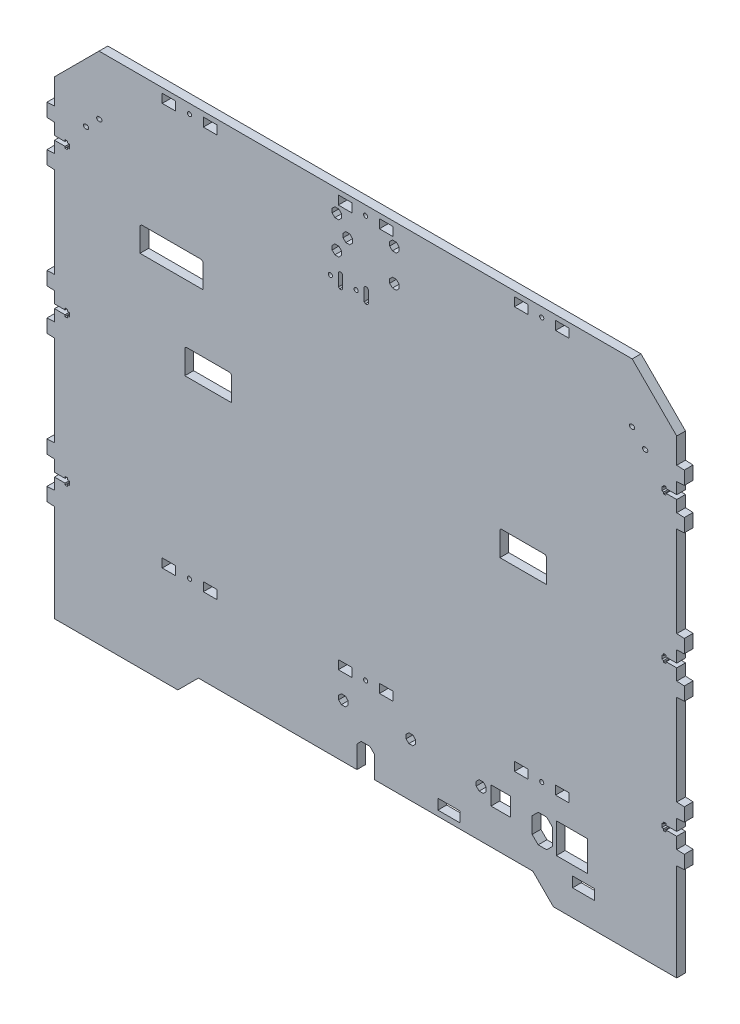
SolidWorks part; units mm, degrees
ref_plane "Front Plane" through (0, 0, 0) normal (0, 0, 1) x (1, 0, 0)
ref_plane "Top Plane" through (0, 0, 0) normal (0, 1, 0) x (1, 0, 0)
ref_plane "Right Plane" through (0, 0, 0) normal (1, 0, 0) x (0, 0, -1)
sketch "Sketch1" plane through (0, 0, 0) normal (0, 0, 1) x (1, 0, 0)
  line L0 (134.7234, -241.5755) -> (134.7234, -247.9755) construction
  line L1 (346.7221, 23.1293) -> (346.7221, 4.6501)
  line L2 (-107.2779, 23.1293) -> (-107.2779, 4.6501)
  line L4 (-96.3779, -120.3749) -> (-97.7779, -120.3749)
  line L5 (11.1227, 52.0245) -> (1.3227, 52.0245)
  line L6 (-28.6786, 45.6245) -> (-28.6786, 52.0245)
  line L7 (-23.7786, 52.0245) -> (-23.7786, 45.6245) construction
  line L8 (11.1227, 45.6245) -> (1.3227, 45.6245)
  line L9 (104.7221, -241.5755) -> (104.7221, -247.9755) construction
  line L10 (6.2227, 52.0245) -> (6.2227, 45.6245) construction
  line L11 (139.6234, -247.9755) -> (139.6234, -241.5755)
  line L12 (129.8234, -247.9755) -> (129.8234, -241.5755)
  line L13 (6.2227, 48.8245) -> (-23.7786, 48.8245) construction
  line L14 (-18.8786, 45.6245) -> (-18.8786, 52.0245)
  line L15 (-28.6786, 52.0245) -> (-18.8786, 52.0245)
  line L16 (1.3227, 45.6245) -> (1.3227, 52.0245)
  line L17 (-28.6786, 45.6245) -> (-18.8786, 45.6245)
  line L18 (11.1227, 45.6245) -> (11.1227, 52.0245)
  line L19 (134.7234, -244.7755) -> (104.7221, -244.7755) construction
  line L20 (139.6227, 52.0245) -> (129.8227, 52.0245)
  line L21 (139.6234, -247.9755) -> (129.8234, -247.9755)
  line L22 (99.8214, 45.6245) -> (99.8214, 52.0245)
  line L23 (104.7214, 52.0245) -> (104.7214, 45.6245) construction
  line L24 (139.6227, 45.6245) -> (129.8227, 45.6245)
  line L25 (109.6221, -247.9755) -> (109.6221, -241.5755)
  line L26 (134.7227, 52.0245) -> (134.7227, 45.6245) construction
  line L27 (99.8221, -241.5755) -> (109.6221, -241.5755)
  line L28 (139.6234, -241.5755) -> (129.8234, -241.5755)
  line L30 (268.1234, -241.5755) -> (258.3234, -241.5755)
  line L31 (99.8221, -247.9755) -> (99.8221, -241.5755)
  line L33 (99.8221, -247.9755) -> (109.6221, -247.9755)
  line L34 (346.722, -319.3255) -> (346.722, -248.4004)
  line L35 (268.1234, -247.9755) -> (268.1234, -241.5755)
  line L36 (314.2269, 55.6245) -> (-74.7828, 55.6245)
  line L37 (134.7227, 48.8245) -> (104.7214, 48.8245) construction
  line L38 (324.0971, 12.6745) -> (324.0971, 3.0745) construction
  line L39 (-84.6529, 12.6745) -> (-84.6529, 3.0745) construction
  line L40 (-74.7828, 55.6245) -> (-107.2779, 23.1293)
  line L41 (314.2269, 55.6245) -> (346.7221, 23.1293)
  line L42 (208.7504, -265.043) -> (199.3504, -274.343) construction
  line L43 (-84.6529, 12.6745) -> (-75.2529, 12.6745) construction
  line L46 (228.3221, -241.5755) -> (238.1221, -241.5755)
  line L47 (109.6214, 45.6245) -> (109.6214, 52.0245)
  line L48 (99.8214, 52.0245) -> (109.6214, 52.0245)
  line L49 (129.8227, 45.6245) -> (129.8227, 52.0245)
  line L50 (99.8214, 45.6245) -> (109.6214, 45.6245)
  line L51 (139.6227, 45.6245) -> (139.6227, 52.0245)
  line L52 (268.1227, 52.0245) -> (258.3227, 52.0245)
  line L53 (102.9071, 3.214) -> (102.0284, 4.0927)
  line L55 (118.6571, -6.0286) -> (118.6571, 3.214)
  line L56 (121.6571, 3.214) -> (121.6571, -6.0286)
  line L57 (228.3214, 45.6245) -> (228.3214, 52.0245)
  line L58 (233.2214, 52.0245) -> (233.2214, 45.6245) construction
  line L59 (228.3221, -247.9755) -> (238.1221, -247.9755)
  line L60 (233.2221, -241.5755) -> (233.2221, -247.9755) construction
  line L63 (258.3234, -247.9755) -> (258.3234, -241.5755)
  line L64 (6.2234, -241.5755) -> (6.2234, -247.9755) construction
  line L65 (-97.7779, -124.6249) -> (-99.5779, -124.6249)
  line L66 (-99.5779, -124.6249) -> (-99.5779, -123.3762)
  line L67 (-112.7779, -25.6249) -> (-107.2779, -25.3499)
  line L69 (-97.7779, -119.1249) -> (-99.5779, -119.1249)
  line L70 (-97.7779, -124.6249) -> (-97.7779, -123.3762)
  line L72 (-99.5779, -119.1249) -> (-99.5779, -120.3749)
  line L74 (-97.7779, -120.3749) -> (-97.7779, -119.1249)
  line L75 (-107.2779, -35.5999) -> (-107.2779, -101.7499)
  line L78 (-99.5779, -123.3762) -> (-107.2779, -123.3762)
  line L81 (-112.7779, -5.3249) -> (-107.2779, -5.5999)
  line L82 (-99.5779, -120.3749) -> (-107.2779, -120.3749)
  line L83 (346.7221, -208.1499) -> (346.7221, -141.9999)
  line L84 (-112.7779, 4.3751) -> (-107.2779, 4.6501)
  line L85 (-99.5779, -16.9762) -> (-107.2779, -16.9762)
  line L87 (-97.7779, -18.2249) -> (-97.7779, -16.9762)
  line L88 (-112.7779, -5.3249) -> (-112.7779, 4.3751)
  line L89 (-96.3779, -16.9762) -> (-97.7779, -16.9762)
  line L90 (-107.2779, -16.9762) -> (-107.2779, -25.3499)
  line L91 (-97.7779, -13.9749) -> (-97.7779, -12.7249)
  line L94 (-97.7779, -12.7249) -> (-99.5779, -12.7249)
  line L95 (-96.3779, -13.9749) -> (-97.7779, -13.9749)
  line L96 (-112.7779, -35.3249) -> (-112.7779, -25.6249)
  line L97 (-99.5779, -13.9749) -> (-107.2779, -13.9749)
  line L98 (-99.5779, -12.7249) -> (-99.5779, -13.9749)
  line L99 (-99.5779, -18.2249) -> (-99.5779, -16.9762)
  line L100 (-97.7779, -18.2249) -> (-99.5779, -18.2249)
  line L101 (-96.3779, -120.3749) -> (-96.3779, -123.3762)
  line L102 (268.1227, 45.6245) -> (258.3227, 45.6245)
  line L103 (11.1234, -247.9755) -> (1.3234, -247.9755)
  line L104 (228.3221, -247.9755) -> (228.3221, -241.5755)
  line L105 (263.2227, 52.0245) -> (263.2227, 45.6245) construction
  line L106 (263.2234, -241.5755) -> (263.2234, -247.9755) construction
  line L108 (-96.3779, -123.3762) -> (-97.7779, -123.3762)
  line L109 (-96.3779, -226.7749) -> (-97.7779, -226.7749)
  line L110 (-96.3779, -13.9749) -> (-96.3779, -16.9762)
  line L111 (-112.7779, -35.3249) -> (-107.2779, -35.5999)
  line L112 (-97.7779, -231.0249) -> (-99.5779, -231.0249)
  line L113 (-99.5779, -231.0249) -> (-99.5779, -229.7762)
  line L114 (-107.2779, -5.5999) -> (-107.2779, -13.9749)
  line L116 (-97.7779, -225.5249) -> (-99.5779, -225.5249)
  line L117 (-97.7779, -231.0249) -> (-97.7779, -229.7762)
  line L118 (11.1234, -247.9755) -> (11.1234, -241.5755)
  line L119 (-99.5779, -225.5249) -> (-99.5779, -226.7749)
  line L121 (-97.7779, -226.7749) -> (-97.7779, -225.5249)
  line L122 (-112.7779, -132.0249) -> (-107.2779, -131.7499)
  line L123 (11.1234, -241.5755) -> (1.3234, -241.5755)
  line L124 (250.7696, -99.7255) -> (251.6221, -100.5755)
  line L126 (-99.5779, -229.7762) -> (-107.2779, -229.7762)
  line L129 (-107.2779, -141.9999) -> (-107.2779, -208.1499)
  line L130 (-99.5779, -226.7749) -> (-107.2779, -226.7749)
  line L133 (-96.3779, -226.7749) -> (-96.3779, -229.7762)
  line L136 (-96.3779, -229.7762) -> (-97.7779, -229.7762)
  line L137 (335.8221, -226.7749) -> (335.8221, -229.7762)
  line L139 (-2.2779, -304.3255) -> (113.3721, -304.3255)
  line L141 (335.8221, -226.7749) -> (337.2221, -226.7749)
  line L143 (346.7221, -13.9749) -> (346.7221, -5.5999)
  line L144 (335.8221, -229.7762) -> (337.2221, -229.7762)
  line L145 (346.7221, -16.9762) -> (346.7221, -25.3499)
  line L147 (339.0221, -225.5249) -> (339.0221, -226.7749)
  line L148 (1.1171, -57.2157) -> (-44.8729, -57.2157)
  line L149 (352.2221, -35.3249) -> (346.7221, -35.5999)
  line L151 (337.2221, -225.5249) -> (339.0221, -225.5249)
  line L153 (337.2221, -231.0249) -> (337.2221, -229.7762)
  line L154 (-44.8729, -57.2157) -> (-44.8729, -39.8207)
  line L155 (337.2221, -231.0249) -> (339.0221, -231.0249)
  line L156 (339.0221, -231.0249) -> (339.0221, -229.7762)
  line L159 (339.0221, -229.7762) -> (346.7221, -229.7762)
  line L160 (339.0221, -226.7749) -> (346.7221, -226.7749)
  line L161 (268.1234, -247.9755) -> (258.3234, -247.9755)
  line L162 (335.8221, -13.9749) -> (335.8221, -16.9762)
  line L163 (337.2221, -226.7749) -> (337.2221, -225.5249)
  line L164 (335.8221, -120.3749) -> (335.8221, -123.3762)
  line L167 (335.8221, -120.3749) -> (337.2221, -120.3749)
  line L168 (337.2221, -18.2249) -> (339.0221, -18.2249)
  line L169 (339.0221, -18.2249) -> (339.0221, -16.9762)
  line L170 (339.0221, -12.7249) -> (339.0221, -13.9749)
  line L171 (339.0221, -13.9749) -> (346.7221, -13.9749)
  line L173 (335.8221, -13.9749) -> (337.2221, -13.9749)
  line L174 (337.2221, -12.7249) -> (339.0221, -12.7249)
  line L175 (238.1221, -247.9755) -> (238.1221, -241.5755)
  line L176 (-17.2779, -319.3255) -> (-2.2779, -304.3255)
  line L177 (337.2221, -13.9749) -> (337.2221, -12.7249)
  line L178 (352.2221, -5.3249) -> (346.7221, -5.5999)
  line L179 (335.8221, -16.9762) -> (337.2221, -16.9762)
  line L180 (352.2221, 4.3751) -> (346.7221, 4.6501)
  line L181 (337.2221, -18.2249) -> (337.2221, -16.9762)
  line L182 (346.7221, -16.9762) -> (346.7221, -25.3499)
  line L183 (339.0221, -16.9762) -> (346.7221, -16.9762)
  line L184 (352.2221, -5.3249) -> (352.2221, 4.3751)
  line L185 (352.2221, -35.3249) -> (352.2221, -25.6249)
  line L186 (335.8221, -123.3762) -> (337.2221, -123.3762)
  line L187 (346.7221, -248.3999) -> (346.722, -248.4004)
  line L189 (339.0221, -119.1249) -> (339.0221, -120.3749)
  line L192 (352.2221, -25.6249) -> (346.7221, -25.3499)
  line L193 (337.2221, -119.1249) -> (339.0221, -119.1249)
  line L195 (337.2221, -124.6249) -> (337.2221, -123.3762)
  line L197 (337.2221, -124.6249) -> (339.0221, -124.6249)
  line L198 (339.0221, -124.6249) -> (339.0221, -123.3762)
  line L199 (346.7221, -35.5999) -> (346.7221, -101.7499)
  line L201 (339.0221, -123.3762) -> (346.7221, -123.3762)
  line L202 (339.0221, -120.3749) -> (346.7221, -120.3749)
  line L203 (263.2234, -244.7755) -> (233.2221, -244.7755) construction
  line L204 (337.2221, -120.3749) -> (337.2221, -119.1249)
  line L205 (0.0221, -38.7257) -> (-43.7779, -38.7257)
  line L206 (1.1171, -57.2157) -> (1.1171, -39.8207)
  line L207 (0.0221, -38.7207) -> (-43.7779, -38.7207)
  line L208 (263.2227, 48.8245) -> (233.2214, 48.8245) construction
  line L209 (-18.8779, -247.9755) -> (-18.8779, -241.5755)
  line L211 (238.1214, 45.6245) -> (238.1214, 52.0245)
  line L212 (-43.7779, -38.7207) -> (-44.8779, -39.8207)
  line L213 (-43.7779, -38.7257) -> (-44.8729, -39.8207)
  line L214 (-28.6779, -247.9755) -> (-28.6779, -241.5755)
  line L215 (217.7196, -100.5755) -> (218.5696, -99.728)
  line L216 (228.3214, 52.0245) -> (238.1214, 52.0245)
  line L217 (258.3227, 45.6245) -> (258.3227, 52.0245)
  line L218 (228.3214, 45.6245) -> (238.1214, 45.6245)
  line L219 (268.1227, 45.6245) -> (268.1227, 52.0245)
  line L220 (217.7196, -100.5755) -> (217.7196, -118.218)
  line L222 (256.2254, -269.5264) -> (256.2254, -281.3396)
  line L223 (156.1726, -266.9051) -> (156.1726, -264.0471)
  line L224 (314.4971, 12.6745) -> (324.0971, 12.6745) construction
  line L225 (218.5696, -99.728) -> (250.7696, -99.728)
  line L226 (1.1221, -57.2252) -> (-44.8779, -57.2252)
  line L229 (-28.6779, -247.9755) -> (-18.8779, -247.9755)
  line L231 (20.8746, -99.7205) -> (21.7271, -100.5705)
  line L232 (-12.1754, -118.213) -> (21.7246, -118.213)
  line L233 (-12.1754, -100.5705) -> (-12.1754, -118.213)
  line L234 (0.0221, -38.7257) -> (1.1171, -39.8207)
  line L235 (-107.2779, -319.3255) -> (-17.2779, -319.3255)
  line L236 (346.722, -319.3255) -> (256.7221, -319.3255)
  line L237 (256.7221, -319.3255) -> (241.7221, -304.3255)
  line L242 (-28.6779, -241.5755) -> (-18.8779, -241.5755)
  line L243 (6.2234, -244.7755) -> (-23.7779, -244.7755) construction
  line L244 (-112.7779, -111.7249) -> (-107.2779, -111.9999)
  line L246 (-23.7779, -241.5755) -> (-23.7779, -247.9755) construction
  line L247 (1.3234, -247.9755) -> (1.3234, -241.5755)
  line L248 (113.3721, -288.1197) -> (113.3721, -304.3255)
  line L249 (126.0721, -288.1197) -> (126.0721, -304.3255)
  line L250 (126.0721, -304.3255) -> (241.7221, -304.3255)
  line L251 (0.0221, -38.7207) -> (1.1221, -39.8207)
  line L252 (149.2726, -264.0471) -> (149.2726, -266.9051)
  line L253 (149.2726, -266.9051) -> (151.2936, -268.9261)
  line L255 (-12.1754, -100.5705) -> (-11.3254, -99.723)
  line L262 (1.1221, -57.2252) -> (1.1221, -39.8207)
  line L266 (-12.1779, -118.2205) -> (21.7271, -118.2205)
  line L268 (154.1516, -268.9261) -> (156.1726, -266.9051)
  line L270 (208.7504, -265.043) -> (199.3504, -265.043) construction
  line L271 (199.3504, -274.343) -> (208.7504, -274.343) construction
  line L272 (208.7504, -274.343) -> (208.7504, -265.043) construction
  line L273 (199.3504, -274.343) -> (199.3504, -265.043) construction
  line L274 (241.2254, -281.3396) -> (241.2254, -269.5264)
  line L275 (256.2254, -269.5264) -> (251.832, -265.133)
  line L276 (100.7857, 4.0927) -> (99.9071, 3.214)
  line L277 (102.0284, -6.9073) -> (100.7857, -6.9073)
  line L278 (126.0721, -288.1197) -> (122.8721, -284.9197)
  line L279 (-11.3254, -99.7205) -> (-12.1779, -100.5705)
  line L280 (-44.8779, -57.2252) -> (-44.8779, -39.8207)
  line L282 (324.0971, 4.5745) -> (323.2971, 4.5745)
  line L283 (-112.7779, -102.0249) -> (-107.2779, -101.7499)
  line L284 (-112.7779, -111.7249) -> (-112.7779, -102.0249)
  line L285 (-75.0529, 11.1745) -> (-74.2529, 11.1745)
  line L286 (-107.2779, -123.3762) -> (-107.2779, -131.7499)
  line L288 (-112.7779, -141.7249) -> (-112.7779, -132.0249)
  line L289 (-112.7779, -141.7249) -> (-107.2779, -141.9999)
  line L290 (-107.2779, -111.9999) -> (-107.2779, -120.3749)
  line L291 (-84.6529, 4.5745) -> (-83.8529, 4.5745)
  line L292 (-112.7779, -238.4249) -> (-107.2779, -238.1499)
  line L294 (-107.2779, -248.3999) -> (-107.2779, -319.3255)
  line L296 (-112.7779, -218.1249) -> (-107.2779, -218.3999)
  line L297 (-75.0529, 14.1745) -> (-74.2529, 14.1745)
  line L298 (-112.7779, -208.4249) -> (-107.2779, -208.1499)
  line L299 (-112.7779, -218.1249) -> (-112.7779, -208.4249)
  line L300 (323.2971, 4.5745) -> (323.2971, 3.0745) construction
  line L302 (352.2221, -141.7249) -> (346.7221, -141.9999)
  line L309 (352.2221, -111.7249) -> (346.7221, -111.9999)
  line L310 (352.2221, -102.0249) -> (346.7221, -101.7499)
  line L311 (352.2221, -111.7249) -> (352.2221, -102.0249)
  line L312 (352.2221, -141.7249) -> (352.2221, -132.0249)
  line L315 (352.2221, -132.0249) -> (346.7221, -131.7499)
  line L317 (346.7221, -123.3762) -> (346.7221, -131.7499)
  line L318 (346.7221, -120.3749) -> (346.7221, -111.9999)
  line L321 (352.2221, -248.1249) -> (346.7221, -248.3999)
  line L322 (-84.6529, 1.5745) -> (-83.8529, 1.5745)
  line L327 (122.8721, -284.9197) -> (116.5721, -284.9197)
  line L328 (352.2221, -218.1249) -> (346.7221, -218.3999)
  line L329 (352.2221, -208.4249) -> (346.7221, -208.1499)
  line L330 (352.2221, -218.1249) -> (352.2221, -208.4249)
  line L331 (352.2221, -248.1249) -> (352.2221, -238.4249)
  line L334 (352.2221, -238.4249) -> (346.7221, -238.1499)
  line L336 (346.7221, -229.7762) -> (346.7221, -238.1499)
  line L337 (346.7221, -226.7749) -> (346.7221, -218.3999)
  line L338 (21.7246, -100.5705) -> (21.7246, -118.213)
  line L339 (-107.2779, -229.7762) -> (-107.2779, -238.1499)
  line L341 (-112.7779, -248.1249) -> (-112.7779, -238.4249)
  line L342 (-112.7779, -248.1249) -> (-107.2779, -248.3999)
  line L343 (-107.2779, -218.3999) -> (-107.2779, -226.7749)
  line L344 (218.5696, -99.7255) -> (250.7696, -99.7255)
  line L345 (251.6221, -100.5755) -> (251.6221, -118.2255)
  line L346 (113.3721, -288.1197) -> (116.5721, -284.9197)
  line L347 (119.7221, 48.8245) -> (119.7221, 42.6245) construction
  line L348 (119.7221, 55.6245) -> (119.7221, 28.1245) construction
  line L349 (119.7221, 28.1245) -> (106.7221, 28.1245) construction
  line L350 (202.5489, -266.068) -> (200.4254, -268.1915)
  line L351 (188.467, -292.8655) -> (188.467, -300.3655)
  line L352 (217.7171, -118.2255) -> (251.6221, -118.2255)
  line L353 (200.4254, -268.1915) -> (200.4254, -271.1946)
  line L354 (217.7196, -118.218) -> (251.6196, -118.218)
  line L355 (200.4254, -271.1946) -> (202.5489, -273.318)
  line L356 (286.697, -292.8655) -> (270.697, -292.8655)
  line L357 (286.697, -292.8655) -> (286.697, -300.3655)
  line L358 (286.697, -300.3655) -> (270.697, -300.3655)
  line L359 (270.697, -292.8655) -> (270.697, -300.3655)
  line L360 (172.467, -292.8655) -> (172.467, -300.3655)
  line L361 (188.467, -300.3655) -> (172.467, -300.3655)
  line L362 (188.467, -292.8655) -> (172.467, -292.8655)
  line L363 (217.7171, -100.5755) -> (217.7171, -118.2255)
  line L364 (202.5489, -273.318) -> (205.5519, -273.318)
  line L365 (324.0971, 12.6745) -> (314.6971, 12.6745) construction
  line L366 (251.6196, -100.5755) -> (251.6196, -118.218)
  line L369 (151.2936, -262.0261) -> (149.2726, -264.0471)
  line L370 (323.2971, 1.5745) -> (324.0971, 1.5745)
  line L371 (314.4971, 14.1745) -> (313.6971, 14.1745)
  line L372 (313.6971, 14.1745) -> (313.6971, 12.6745) construction
  line L373 (313.6971, 11.1745) -> (314.4971, 11.1745)
  line L374 (205.5519, -273.318) -> (207.6754, -271.1946)
  line L376 (207.6754, -271.1946) -> (207.6754, -268.1915)
  line L377 (-11.3254, -99.723) -> (20.8746, -99.723)
  line L378 (21.7246, -100.5705) -> (20.8746, -99.723)
  line L380 (21.7271, -100.5705) -> (21.7271, -118.2205)
  line L381 (154.1516, -262.0261) -> (151.2936, -262.0261)
  line L382 (281.7421, -263.8773) -> (281.7421, -285.8887)
  line L383 (281.7421, -285.8887) -> (258.8887, -285.8887)
  line L384 (258.8887, -285.8887) -> (258.8887, -263.8773)
  line L385 (258.8887, -263.8773) -> (281.7421, -263.8773)
  line L386 (-11.3254, -99.7205) -> (20.8746, -99.7205)
  line L387 (207.6754, -268.1915) -> (205.5519, -266.068)
  line L389 (211.2129, -278.433) -> (211.2129, -265.033)
  line L390 (211.2129, -278.433) -> (225.2779, -278.433)
  line L391 (225.2779, -278.433) -> (225.2779, -265.033)
  line L392 (211.2129, -265.033) -> (225.2779, -265.033)
  line L393 (256.2254, -281.3396) -> (251.832, -285.733)
  line L394 (251.832, -285.733) -> (245.6188, -285.733)
  line L395 (245.6188, -285.733) -> (241.2254, -281.3396)
  line L396 (245.6188, -265.133) -> (241.2254, -269.5264)
  line L397 (205.5519, -266.068) -> (202.5489, -266.068)
  line L400 (156.1726, -264.0471) -> (154.1516, -262.0261)
  line L401 (151.2936, -268.9261) -> (154.1516, -268.9261)
  line L404 (218.5696, -99.7255) -> (217.7171, -100.5755)
  line L406 (105.293, 31.5745) -> (103.2721, 29.5535)
  line L410 (-12.1779, -100.5705) -> (-12.1779, -118.2205)
  line L414 (103.2721, 29.5535) -> (103.2721, 26.6954)
  line L415 (103.2721, 26.6954) -> (105.293, 24.6745)
  line L416 (105.293, 24.6745) -> (108.1511, 24.6745)
  line L417 (108.1511, 24.6745) -> (110.1721, 26.6954)
  line L418 (110.1721, 26.6954) -> (110.1721, 29.5535)
  line L419 (110.1721, 29.5535) -> (108.1511, 31.5745)
  line L420 (108.1511, 31.5745) -> (105.293, 31.5745)
  line L421 (102.9071, -6.0286) -> (102.0284, -6.9073)
  line L422 (121.6571, 3.214) -> (120.7784, 4.0927)
  line L423 (120.7784, 4.0927) -> (119.5357, 4.0927)
  line L424 (119.5357, 4.0927) -> (118.6571, 3.214)
  line L425 (102.9071, 3.214) -> (102.9071, -6.0286)
  line L426 (120.7784, -6.9073) -> (119.5357, -6.9073)
  line L427 (100.7857, -6.9073) -> (99.9071, -6.0286)
  line L428 (95.2721, 17.8035) -> (95.2721, 14.9454)
  line L429 (97.293, 12.9245) -> (100.1511, 12.9245)
  line L430 (102.1721, 14.9454) -> (102.1721, 17.8035)
  line L431 (100.1511, 19.8245) -> (97.293, 19.8245)
  line L432 (100.1511, 12.9245) -> (102.1721, 14.9454)
  line L433 (102.1721, 17.8035) -> (100.1511, 19.8245)
  line L434 (97.293, 19.8245) -> (95.2721, 17.8035)
  line L435 (95.2721, 14.9454) -> (97.293, 12.9245)
  line L436 (95.2721, 41.3035) -> (95.2721, 38.4454)
  line L437 (97.293, 36.4245) -> (100.1511, 36.4245)
  line L438 (102.1721, 38.4454) -> (102.1721, 41.3035)
  line L439 (100.1511, 43.3245) -> (97.293, 43.3245)
  line L440 (100.1511, 36.4245) -> (102.1721, 38.4454)
  line L441 (102.1721, 41.3035) -> (100.1511, 43.3245)
  line L442 (97.293, 43.3245) -> (95.2721, 41.3035)
  line L443 (95.2721, 38.4454) -> (97.293, 36.4245)
  line L444 (137.2721, 41.3035) -> (137.2721, 38.4454)
  line L445 (139.293, 36.4245) -> (142.1511, 36.4245)
  line L446 (144.1721, 38.4454) -> (144.1721, 41.3035)
  line L447 (142.1511, 43.3245) -> (139.293, 43.3245)
  line L448 (142.1511, 36.4245) -> (144.1721, 38.4454)
  line L449 (144.1721, 41.3035) -> (142.1511, 43.3245)
  line L450 (139.293, 43.3245) -> (137.2721, 41.3035)
  line L451 (137.2721, 38.4454) -> (139.293, 36.4245)
  line L452 (137.2721, 17.8035) -> (137.2721, 14.9454)
  line L453 (139.293, 12.9245) -> (142.1511, 12.9245)
  line L454 (144.1721, 14.9454) -> (144.1721, 17.8035)
  line L455 (142.1511, 19.8245) -> (139.293, 19.8245)
  line L456 (142.1511, 12.9245) -> (144.1721, 14.9454)
  line L457 (144.1721, 17.8035) -> (142.1511, 19.8245)
  line L458 (139.293, 19.8245) -> (137.2721, 17.8035)
  line L459 (137.2721, 14.9454) -> (139.293, 12.9245)
  line L460 (100.0221, -264.0465) -> (100.0221, -266.9046)
  line L461 (102.043, -268.9255) -> (104.9011, -268.9255)
  line L462 (106.9221, -266.9046) -> (106.9221, -264.0465)
  line L463 (104.9011, -262.0255) -> (102.043, -262.0255)
  line L464 (104.9011, -268.9255) -> (106.9221, -266.9046)
  line L465 (106.9221, -264.0465) -> (104.9011, -262.0255)
  line L466 (102.043, -262.0255) -> (100.0221, -264.0465)
  line L467 (100.0221, -266.9046) -> (102.043, -268.9255)
  line L468 (99.9071, -6.0286) -> (99.9071, 3.214)
  line L469 (102.0284, 4.0927) -> (100.7857, 4.0927)
  line L470 (119.5357, -6.9073) -> (118.6571, -6.0286)
  line L471 (121.6571, -6.0286) -> (120.7784, -6.9073)
  line L473 (251.832, -265.133) -> (245.6188, -265.133)
  line L480 (251.6196, -100.5755) -> (250.7696, -99.728)
  circle A0 centre (-8.7779, 48.8245) radius 1.5
  circle A1 centre (119.7227, -244.7755) radius 1.5
  circle A2 centre (248.2221, 48.8245) radius 1.5
  circle A3 centre (248.2227, -244.7755) radius 1.5
  circle A4 centre (204.0504, -269.693) radius 3.625 construction
  circle A5 centre (119.7221, 48.8245) radius 1.5
  circle A6 centre (152.7226, -265.4761) radius 3.45 construction
  circle A7 centre (120.1571, 2.5927) radius 1.5 construction
  circle A8 centre (-84.6529, 12.6745) radius 4.9 construction
  circle A9 centre (101.4071, 2.5927) radius 1.5 construction
  circle A10 centre (106.7221, 28.1245) radius 3.45 construction
  circle A11 centre (324.0971, 12.6745) radius 4.9 construction
  circle A13 centre (98.7221, 16.3745) radius 3.45 construction
  circle A14 centre (98.7221, 39.8745) radius 3.45 construction
  circle A16 centre (140.7221, 39.8745) radius 3.45 construction
  circle A17 centre (140.7221, 16.3745) radius 3.45 construction
  circle A18 centre (103.4721, -265.4755) radius 3.45 construction
  circle A20 centre (-8.7773, -244.7755) radius 1.5
  circle A38 centre (112.7821, -1.5073) radius 1.5
  arc A41 (-84.6529, 4.5745) -> (-84.6529, 1.5745) centre (-84.6529, 3.0745) ccw
  circle A42 centre (94.0321, -1.5073) radius 1.5
  arc A43 (-74.2529, 11.1745) -> (-74.2529, 14.1745) centre (-74.1529, 12.6745) ccw
  arc A47 (-75.0529, 14.1745) -> (-75.0529, 11.1745) centre (-75.0529, 12.6745) ccw
  arc A48 (-83.8529, 1.5745) -> (-83.8529, 4.5745) centre (-83.8529, 3.0745) ccw
  arc A52 (324.0971, 4.5745) -> (324.0971, 1.5745) centre (324.0971, 3.0745) cw
  arc A57 (314.4971, 14.1745) -> (314.4971, 11.1745) centre (314.4971, 12.6745) cw
  arc A58 (323.2971, 4.5745) -> (323.2971, 1.5745) centre (323.2971, 3.0745) ccw
  arc A59 (313.6971, 14.1745) -> (313.6971, 11.1745) centre (313.6971, 12.6745) ccw
  point P0 (0, 0)
  point P2 (-43.8779, -50.2207)
  point P216 (-3.8829, -68.7157)
  point P228 (-43.8729, -68.7157)
  point P229 (-43.8729, -50.2257)
  point P230 (-3.8829, -50.2257)
  point P231 (-43.8779, -68.7207)
  point P234 (-3.8779, -68.7207)
  point P236 (119.7221, -284.9197)
  point P260 (-3.8779, -50.2207)
  point P361 (547.2436, -78.2135)
  point P363 (581.1436, -78.2185)
  point P364 (547.2386, -78.2185)
  point P375 (547.2386, -59.2185)
  point P378 (581.1436, -59.2185)
  point P381 (581.1386, -78.2135)
  point P383 (581.1386, -59.2235)
  point P402 (547.2436, -59.2235)
  dimension "D17" = 6.4
  dimension "D4" = 30.0014
  dimension "D26" = 16
  dimension "D28" = 7.5
  dimension "D23" = 60.025
  dimension "D30" = 16
  dimension "D32" = 98.23
  dimension "D33" = 9.8
  dimension "D5" = 30.0014
  dimension "D10" = 3.2
  dimension "D12" = 9.6
  dimension "D13" = 9.6
  dimension "D18" = 9.8
  dimension "D19" = 6.4
  dimension "D21" = 9.8
  dimension "D22" = 30.0014
  dimension "D24" = 6.4
  dimension "D31" = 7.5
extrude "Boss-Extrude1" add sketch "Sketch1" along normal blind 6.4
sketch "Sketch3" plane through (0, 0, 0) normal (0, 0, -1) x (-1, 0, 0)
  line L0 (-331.8875, -299.397) -> (-346.722, -299.397) construction
  line L1 (-346.722, -319.3255) -> (-346.722, -248.4004) construction
  line L2 (-337.1024, -278.6404) -> (-346.722, -278.6404) construction
  text T0 "0000000M" font "Century Gothic" height 5.5
  text T1 "Brooklyn" font "Lucida Bright" height 7.5
  dimension "D1" = 9.6197
  dimension "D2" = 14.8346
extrude "Cut-Extrude1" cut sketch "Sketch3" against normal blind 0.2
sketch "Sketch4" plane through (0, 0, 0) normal (0, 0, -1) x (-1, 0, 0)
  line L1 (-286.9465, -263.8773) -> (-342.1479, -263.8773)
  line L2 (-286.9465, -263.8773) -> (-286.9465, -285.8887)
  line L3 (-286.9465, -285.8887) -> (-342.1479, -285.8887)
  line L4 (-342.1479, -263.8773) -> (-342.1479, -285.8887)
extrude "Cut-Extrude2" cut sketch "Sketch4" against normal blind 0.1
